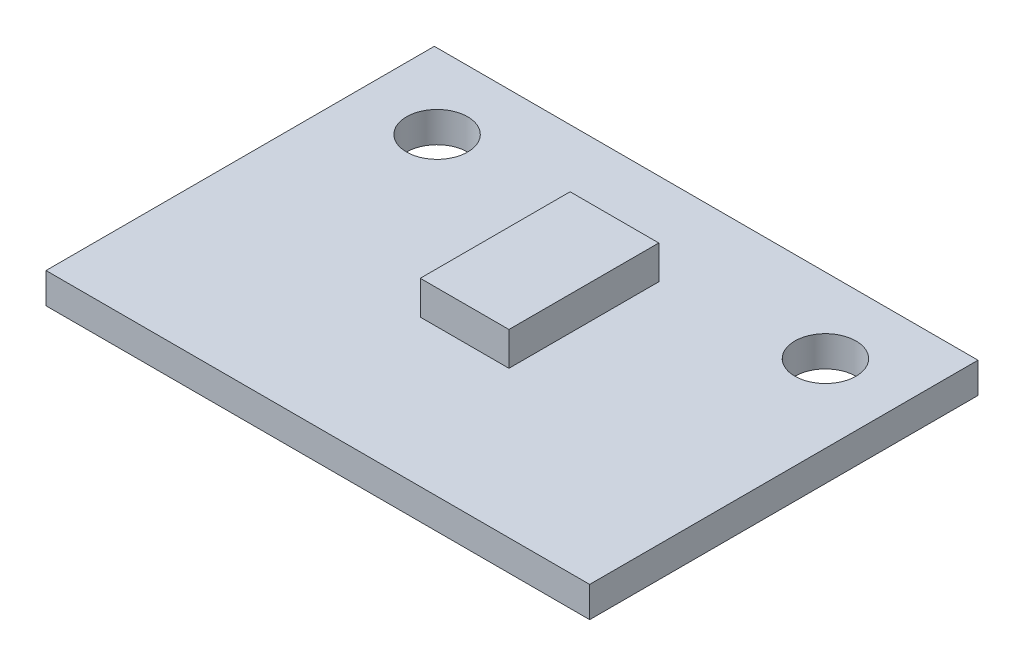
SolidWorks part; units mm, degrees
ref_plane "Front Plane" through (0, 0, 0) normal (0, 0, 1) x (1, 0, 0)
ref_plane "Top Plane" through (0, 0, 0) normal (0, 1, 0) x (1, 0, 0)
ref_plane "Right Plane" through (0, 0, 0) normal (1, 0, 0) x (0, 0, -1)
sketch "草图1" plane through (0, 0, 0) normal (0, 1, 0) x (1, 0, 0)
  line L0 (-6.35, 3.9) -> (6.35, 3.9) construction
  line L1 (-8.89, -6.35) -> (8.89, -6.35)
  line L2 (-8.89, -6.35) -> (-8.89, 6.35)
  line L3 (-8.89, 6.35) -> (8.89, 6.35)
  line L4 (8.89, -6.35) -> (8.89, 6.35)
  line L5 (-8.89, -6.35) -> (8.89, 6.35) construction
  line L6 (-8.89, 6.35) -> (8.89, -6.35) construction
  line L7 (-1.45, -1.55) -> (1.45, -1.55)
  line L8 (-1.45, -1.55) -> (-1.45, 3.35)
  line L9 (-1.45, 3.35) -> (1.45, 3.35)
  line L10 (1.45, -1.55) -> (1.45, 3.35)
  line L11 (-1.45, -1.55) -> (1.45, 3.35) construction
  line L12 (-1.45, 3.35) -> (1.45, -1.55) construction
  line L13 (0, 0) -> (0, 6.35) construction
  circle A0 centre (-6.35, 3.9) radius 1
  circle A1 centre (6.35, 3.9) radius 1
  point P0 (0, 0)
  point P6 (0, 0.9)
  point P17 (0, 0)
  point P18 (-6.8597, 3.817)
  point P19 (0, 0.9)
  dimension "D6" = 2
  dimension "D8" = 12.7
  dimension "D7" = 2.45
  dimension "D1" = 17.78
  dimension "D2" = 12.7
  dimension "D3" = 3
  dimension "D4" = 4.9
  dimension "D5" = 2.9
extrude "凸台-拉伸1" add sketch "草图1" along normal blind 1 contours L7 L10 L9 L8 | L1 L4 L3 L2 A1 A0 L10 L7 L8 L9 region at (-8.6715, 0, 0) region at (0, 0, -0.9)
extrude "凸台-拉伸2" add sketch "草图1<3>" along normal offset from surface (2.1 mm away) 1.1 contours L7 L10 L9 L8 region at (0, 0, -0.9) up to face at (6.35, 1, -2.9) offset beyond the face yes
sketch "草图1<3>" plane through (0, 0, 0) normal (0, 1, 0) x (1, 0, 0) same geometry as "草图1"
